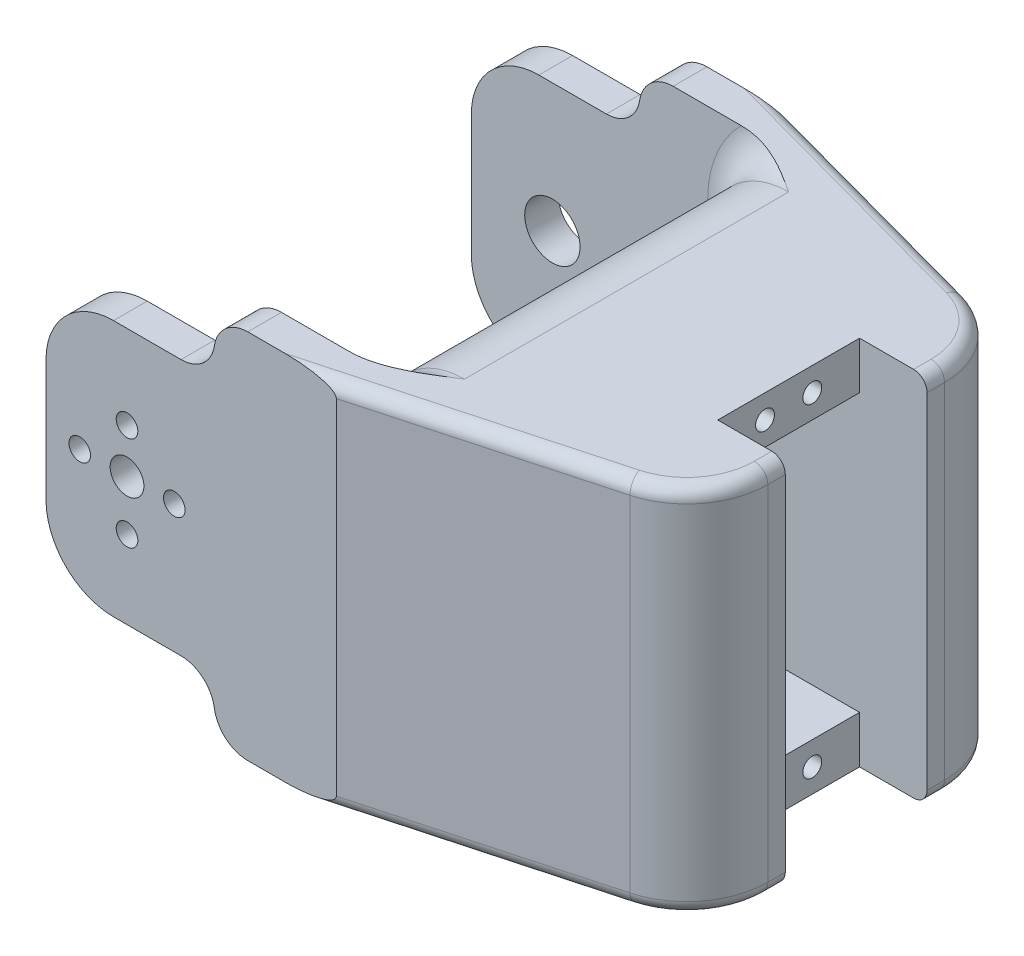
SolidWorks part; units mm, degrees
ref_plane "Front Plane" through (0, 0, 0) normal (0, 0, 1) x (1, 0, 0)
ref_plane "Top Plane" through (0, 0, 0) normal (0, 1, 0) x (1, 0, 0)
ref_plane "Right Plane" through (0, 0, 0) normal (1, 0, 0) x (0, 0, -1)
sketch "Sketch1" plane through (0, 0, 0) normal (0, 1, 0) x (1, 0, 0)
  line L2 (34, -58) -> (0, -58)
  line L3 (0, 5) -> (80, 5)
  line L4 (80, 5) -> (80, -63)
  line L5 (80, -63) -> (0, -63)
  line L8 (0, 0) -> (34, 0)
  line L9 (34, 0) -> (34, -58)
  line L10 (0, 5) -> (-6, 5)
  line L11 (0, 0) -> (75, 0) construction
  line L12 (75, 0) -> (75, -58) construction
  line L13 (75, -58) -> (0, -58) construction
  line L14 (-6, 5) -> (-6, 0)
  line L15 (-6, 0) -> (0, 0)
  line L16 (0, -63) -> (-6, -63)
  line L17 (-6, -63) -> (-6, -58)
  line L18 (-6, -58) -> (0, -58)
  dimension "D1" = 5
extrude "Boss-Extrude1" add sketch "Sketch1" along normal blind 55
sketch "Sketch2" plane through (80, 0, 0) normal (1, 0, 0) x (0, 0, -1)
  line L0 (-29, 55) -> (-29, 0)
  line L1 (-63, 55) -> (5, 55) construction
  line L2 (-63, 0) -> (5, 0) construction
  line L3 (-29, 27.5) -> (-29, 51.5)
  line L4 (-18.5, 7) -> (-39.5, 7)
  line L5 (-18.5, 7) -> (-18.5, 48)
  line L6 (-18.5, 48) -> (-39.5, 48)
  line L7 (-39.5, 7) -> (-39.5, 48)
  line L8 (-18.5, 7) -> (-39.5, 48) construction
  line L9 (-18.5, 48) -> (-39.5, 7) construction
  circle A0 centre (-32.5, 51.5) radius 1.4
  circle A1 centre (-32.5, 3.5) radius 1.4
  circle A2 centre (-25.5, 3.5) radius 1.4
  circle A3 centre (-25.5, 51.5) radius 1.4
  point P6 (-29, 27.5)
extrude "Cut-Extrude1" cut sketch "Sketch2" against normal blind 40 contours L5 L6 L3 L0 L4 | L7 L4 L0 L3 L6 | A3 | A0 | A2 | A1 region at (80, 27.5, 23.75) region at (80, 27.5, 34.25) region at (80, 51.5, 32.5) region at (80, 3.5, 32.5) region at (80, 3.5, 25.5) region at (80, 51.5, 25.5)
sketch "Sketch3" plane through (0, 0, 0) normal (0, -1, 0) x (1, 0, 0)
  line L0 (80, 29) -> (40, 29)
  line L1 (80, 63) -> (80, -5) construction
  line L2 (40, 29) -> (40, 32)
  line L3 (40, 32) -> (62.7454, 32)
  line L4 (62.7454, 32) -> (62.7454, 23)
  line L5 (62.7454, 23) -> (40, 23)
  line L6 (40, 23) -> (40, 29)
extrude "Cut-Extrude2" cut sketch "Sketch3" against normal blind 32 contours L6 L5 L4 L0 | L4 L3 L2 L0 region at (51.3727, 0, 26) region at (51.3727, 0, 30.5)
sketch "Sketch4" plane through (80, 0, 0) normal (1, 0, 0) x (0, 0, -1)
  line L0 (-39.5, 48) -> (-39.5, 55)
  line L1 (-63, 55) -> (5, 55) construction
  line L2 (-18.5, 7) -> (-18.5, 0)
  line L3 (-63, 0) -> (5, 0) construction
  line L5 (-39.5, 55) -> (-18.5, 55)
  line L6 (-39.5, 55) -> (-39.5, 0)
  line L7 (-39.5, 0) -> (-18.5, 0)
  line L8 (-18.5, 55) -> (-18.5, 0)
  circle M5 centre (-25.5, 3.5) radius 1.4
  circle M6 centre (-32.5, 51.5) radius 1.4
  line M7 (-39.5, 48) -> (-18.5, 48)
  line M8 (-18.5, 48) -> (-18.5, 7)
  line M9 (-18.5, 7) -> (-39.5, 7)
  line M10 (-39.5, 7) -> (-39.5, 48)
  line M11 (-63, 0) -> (5, 0)
  line M13 (5, 55) -> (-63, 55)
  circle M15 centre (-25.5, 51.5) radius 1.4
  circle M16 centre (-32.5, 3.5) radius 1.4
extrude "Cut-Extrude3" cut sketch "Sketch4" against normal blind 10 contours M7 M10 M9 M8 | L8 L0 M13 M7 M15 M6 | L6 L2 M9 M11 M16 M5 region at (80, 27.5, 29) region at (80, 51.5, 29) region at (80, 3.5, 29)
sketch "Sketch5" plane through (0, 0, 0) normal (0, -1, 0) x (1, 0, 0)
  line L0 (80, 39.5) -> (80, 51.25)
  line L1 (80, 63) -> (80, 39.5) construction
  line L2 (80, 51.25) -> (37, 63)
  line L3 (-6, 63) -> (80, 63) construction
  line L4 (37, 63) -> (80, 63)
  line L5 (80, 63) -> (80, 51.25)
  line L6 (80, 6.75) -> (37, -5)
  line L7 (80, 18.5) -> (80, -5) construction
  line L8 (80, -5) -> (-6, -5) construction
  line L9 (37, -5) -> (80, -5)
  line L10 (80, -5) -> (80, 6.75)
  line M5 (80, -5) -> (80, 18.5)
  line M9 (80, 39.5) -> (80, 63)
  line M10 (80, 63) -> (-6, 63)
  line M16 (-6, -5) -> (80, -5)
extrude "Cut-Extrude4" cut sketch "Sketch5" against normal blind 87 contours L6 M5 M16 | L2 M9 M10 region at (65.6667, 0, 59.0833) region at (65.6667, 0, -1.0833)
sketch "Sketch6" plane through (0, 0, 63) normal (0, 0, 1) x (1, 0, 0)
  circle A1 centre (-1, 27.5) radius 1.6
  circle A2 centre (6, 27.5) radius 2.5
  circle A3 centre (6, 34.0814) radius 1.6
  circle A4 centre (13, 27.5) radius 1.6
  circle A5 centre (6, 20.0814) radius 1.6
extrude "Cut-Extrude5" cut sketch "Sketch6" against normal blind 10 contours A5 | A2 | A4 | A3 | A1
fillet "Fillet3" radius 12 4 edges at (34, 0, 29) (34, 55, 29) (80, 27.5, 6.75) (80, 27.5, 51.25)
fillet "Fillet5" radius 2 12 edges at (80, 0, 17.2054) (77.5383, 0, 8.6293) (80, 0, 40.7946) (77.5383, 0, 49.3707) (80, 55, 40.7946) (77.5383, 55, 49.3707) (80, 55, 17.2054) (77.5383, 55, 8.6293) (54.0816, 0, -0.3324) (54.0816, 0, 58.3324) (54.0816, 55, 58.3324) (54.0816, 55, -0.3324)
sketch "Sketch7" plane through (0, 0, -5) normal (0, 0, -1) x (-1, 0, 0)
  circle A0 centre (-6, 27.5) radius 4.1
extrude "Cut-Extrude6" cut sketch "Sketch7" against normal blind 10 contours A0
sketch "Sketch8" plane through (0, 0, -5) normal (0, 0, -1) x (-1, 0, 0)
  line L0 (6, 27.5) -> (6, 46.5)
  line L1 (6, 55) -> (6, 0) construction
  line L2 (6, 46.5) -> (-19, 46.5)
  line L3 (-19, 46.5) -> (-19, 55)
  line L4 (-29.4125, 55) -> (6, 55) construction
  line L5 (-19, 0) -> (-19, 8.5)
  line L6 (-29.4125, 0) -> (6, 0) construction
  line L7 (-19, 8.5) -> (6, 8.5)
  line L8 (6, 8.5) -> (6, 27.5)
  line L9 (-19, 0) -> (6, 0)
  line L10 (6, 0) -> (6, 8.5)
  line L11 (-19, 55) -> (6, 55)
  line L12 (6, 55) -> (6, 46.5)
  line M7 (-29.4125, 0) -> (6, 0)
  line M8 (6, 0) -> (6, 55)
  line M9 (6, 55) -> (-29.4125, 55)
extrude "Cut-Extrude7" cut sketch "Sketch8" against normal blind 98 contours L3 L2 M8 M9 | L7 L5 M7 M8 region at (6.5, 50.75, -5) region at (6.5, 4.25, -5)
fillet "Fillet6" radius 5 6 edges at (37.5147, 51.4853, 58) (37.5147, 3.5147, 58) (37.5147, 51.4853, 0) (37.5147, 3.5147, 0) (34, 27.5, 58) (34, 27.5, 0)
fillet "Fillet7" radius 5 1 edges at (19, 0, -2.5)
fillet "Fillet8" radius 5 4 edges at (19, 8.5, -2.5) (19, 46.5, -2.5) (19, 46.5, 60.5) (19, 8.5, 60.5)
fillet "Fillet9" radius 5 3 edges at (19, 0, 60.5) (19, 55, 60.5) (19, 55, -2.5)
fillet "Fillet10" radius 10 4 edges at (-6, 8.5, 60.5) (-6, 46.5, 60.5) (-6, 8.5, -2.5) (-6, 46.5, -2.5)
